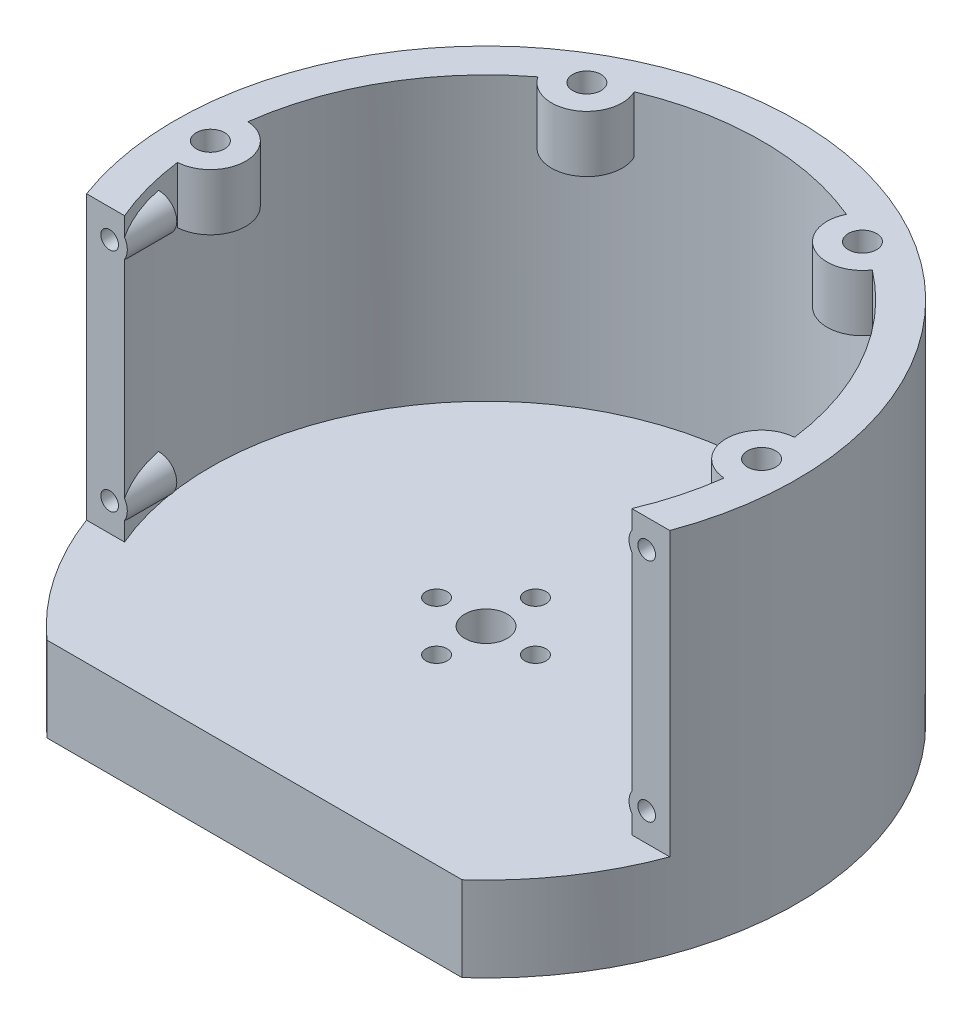
SolidWorks part; units mm, degrees
ref_plane "Спереди" through (0, 0, 0) normal (0, 0, 1) x (1, 0, 0)
ref_plane "Сверху" through (0, 0, 0) normal (0, 1, 0) x (1, 0, 0)
ref_plane "Справа" through (0, 0, 0) normal (1, 0, 0) x (0, 0, -1)
sketch "Эскиз6" plane through (0, 0, 0) normal (1, 0, 0) x (0, 0, -1)
  line L0 (26, 0) -> (44, 0)
  line L1 (0, 0) -> (0, 77.627) construction
  line L2 (44, 0) -> (44, 52)
  line L3 (44, 52) -> (39, 52)
  line L4 (39, 52) -> (39, 12)
  line L5 (39, 12) -> (0, 12)
  line L6 (0, 12) -> (0, 7)
  line L7 (0, 7) -> (26, 7)
  line L8 (26, 7) -> (26, 0)
  dimension "D1" = 5
  dimension "D2" = 26
  dimension "D3" = 52
  dimension "D4" = 44
  dimension "D5" = 7
revolve "Повернуть1" add sketch "Эскиз6" angle 360 about L1
sketch "Эскиз9" plane through (0, 0, 0) normal (0, 1, 0) x (1, 0, 0)
  circle A0 centre (0, 0) radius 3
  circle A1 centre (0, 0) radius 7 construction
  circle A2 centre (0, 7) radius 1.5
  circle A3 centre (7, 0) radius 1.5
  circle A4 centre (0, -7) radius 1.5
  circle A5 centre (-7, 0) radius 1.5
  point P15 (0, 0)
  dimension "D1" = 4
extrude "Вырез-Вытянуть1" cut sketch "Эскиз9" along normal up to surface (12 mm away) from offset 7 up to face at (0, 12, -39)
ref_plane "Плоскость1" through (0, 0, 45) normal (0, 0, 1) x (1, 0, 0)
sketch "Эскиз14" plane through (0, 0, 0) normal (0, 1, 0) x (1, 0, 0)
  line L0 (36, -15) -> (-36, -15)
  arc A0 (36, -15) -> (-36, -15) centre (0, 0) cw
  circle A1 centre (0, 0) radius 39 construction
  circle A2 centre (0, 0) radius 39 construction
  dimension "D1" = 15
extrude "Бобышка-Вытянуть6" [suppressed] add sketch "Эскиз14" against normal up to surface (38 mm away) from offset 50
sketch "Эскиз17" plane through (0, 0, 45) normal (0, 0, 1) x (1, 0, 0)
  line L0 (36, 52) -> (-36, 52)
  line L1 (44, 52) -> (-44, 52) construction
  line L2 (-37.4166, 0) -> (37.4166, 0)
  line L3 (-44, 0) -> (44, 0) construction
  arc A0 (-36, 52) -> (-37.4166, 0) centre (0, 25) ccw
  arc A1 (37.4166, 0) -> (36, 52) centre (0, 25) ccw
  dimension "D1" = 90
  dimension "D2" = 25
extrude "Бобышка-Вытянуть15" [suppressed] add sketch "Эскиз17" against normal up to surface (30 mm away)
sketch "Эскиз11" plane through (0, 0, 45) normal (0, 0, 1) x (1, 0, 0)
  line L0 (-44, 0) -> (44, 0) construction
  line L1 (-30, 35) -> (10, 35)
  line L2 (-30, 35) -> (-30, 15)
  line L3 (-30, 15) -> (10, 15)
  line L4 (10, 35) -> (10, 15)
  dimension "D1" = 20
  dimension "D2" = 40
  dimension "D3" = 15
  dimension "D4" = 30
extrude "Вырез-Вытянуть2" [suppressed] cut sketch "Эскиз11" against normal blind 50 and the other way blind 150
sketch "Эскиз15" plane through (0, 0, 45) normal (0, 0, 1) x (1, 0, 0)
  line L1 (-37, 37) -> (17, 37)
  line L2 (-37, 37) -> (-37, 17)
  line L3 (-37, 17) -> (17, 17)
  line L4 (17, 37) -> (17, 17)
  line L6 (44, 52) -> (-44, 52) construction
  dimension "D1" = 54
  dimension "D2" = 20
  dimension "D3" = 15
  dimension "D4" = 37
extrude "Вырез-Вытянуть5" [suppressed] cut sketch "Эскиз15" against normal blind 27 from offset 28 offset against normal yes
sketch "Эскиз19" plane through (0, 0, 45) normal (0, 0, 1) x (1, 0, 0)
  circle A0 centre (0, 25) radius 12
  dimension "D1" = 24
extrude "Вырез-Вытянуть7" [suppressed] cut sketch "Эскиз19" against normal up to surface and the other way blind 5
sketch "Эскиз20" [suppressed] plane through (0, 0, 0) normal (0, 1, 0) x (1, 0, 0)
  line L0 (-45, -30) -> (45, -30)
  line L1 (-45, -45) -> (-45, -30)
  line L2 (-45, 0) -> (-45, -45) construction
  line L3 (-45, -45) -> (45, -45)
  line L4 (37.4166, -45) -> (45, -45) construction
  line L5 (45, -45) -> (45, -30)
  line L6 (45, -45) -> (45, 0) construction
  dimension "D1" = 15
extrude "Вырез-Вытянуть8" [suppressed] cut sketch "Эскиз20" along normal blind 50
sketch "Эскиз21" plane through (0, 0, 0) normal (0, 1, 0) x (1, 0, 0)
  line L0 (41.2692, -15.2595) -> (-41.2692, -15.2595)
  arc A0 (41.2692, -15.2595) -> (-41.2692, -15.2595) centre (0, 0) cw
  dimension "D1" = 44
extrude "Вырез-Вытянуть9" cut sketch "Эскиз21" against normal blind 43 from offset 55
sketch "Эскиз22" plane through (0, 0, 15.2595) normal (0, 0, 1) x (1, 0, 0)
  line L0 (-44, 0) -> (44, 0) construction
  line L5 (-38, 48) -> (38, 48) construction
  line L6 (-38, 48) -> (-38, 16) construction
  line L7 (-38, 16) -> (38, 16) construction
  line L8 (38, 48) -> (38, 16) construction
  circle A3 centre (-38, 16) radius 2.5
  circle A4 centre (-38, 48) radius 2.5
  circle A5 centre (38, 48) radius 2.5
  circle A6 centre (38, 16) radius 2.5
  dimension "D1" = 32
  dimension "D2" = 76
  dimension "D3" = 16
  dimension "D4" = 5
  dimension "D6" = 5
  dimension "D7" = 5
  dimension "D8" = 5
  dimension "D5" = 38
sketch "Эскиз23" plane through (0, 12, 0) normal (0, 1, 0) x (1, 0, 0)
  line L0 (-29.3737, -32.7595) -> (29.3737, -32.7595)
  line L1 (41.2692, -15.2595) -> (35.8908, -15.2595) construction
  arc A0 (-41.2692, -15.2595) -> (41.2692, -15.2595) centre (0, 0) ccw construction
  arc A1 (29.3737, -32.7595) -> (-29.3737, -32.7595) centre (0, 0) cw
  dimension "D1" = 17.5
extrude "Вырез-Вытянуть11" cut sketch "Эскиз23" against normal through all
sketch "Эскиз25" plane through (0, 52, 0) normal (0, 1, 0) x (1, 0, 0)
  arc A0 (-38.6795, -4.9897) -> (-38.6795, 4.9897) centre (-39, 0) ccw
  arc A1 (35.8908, -15.2595) -> (-35.8908, -15.2595) centre (0, 0) ccw construction
  arc A2 (35.8908, -15.2595) -> (-35.8908, -15.2595) centre (0, 0) ccw construction
  arc A3 (-38.6795, 4.9897) -> (-38.6795, -4.9897) centre (0, 0) ccw
extrude "Бобышка-Вытянуть17" add sketch "Эскиз25" against normal blind 8
sketch "Эскиз26" plane through (0, 52, 0) normal (0, 1, 0) x (1, 0, 0)
  circle A0 centre (-39, 0) radius 2
  circle A1 centre (0, 0) radius 39 construction
  dimension "D1" = 4
extrude "Вырез-Вытянуть12" cut sketch "Эскиз26" against normal blind 5
pattern_circular "Круговой массив3" count 4 every 60 about axis through (0, 52, 0) along (0, -1, 0) of "Бобышка-Вытянуть17", "Вырез-Вытянуть12"
extrude "Бобышка-Вытянуть19" add sketch "Эскиз22" against normal blind 7
sketch "Эскиз28" plane through (0, 0, 15.2595) normal (0, 0, 1) x (1, 0, 0)
  line L5 (-38, 48) -> (38, 48) construction
  line L6 (-38, 48) -> (-38, 16) construction
  line L7 (-38, 16) -> (38, 16) construction
  line L8 (38, 48) -> (38, 16) construction
  circle A3 centre (-38, 16) radius 1.25
  circle A4 centre (-38, 48) radius 1.25
  circle A5 centre (38, 48) radius 1.25
  circle A6 centre (38, 16) radius 1.25
  dimension "D1" = 32
  dimension "D2" = 76
  dimension "D4" = 2.5
  dimension "D6" = 2.5
  dimension "D7" = 2.5
  dimension "D8" = 2.5
extrude "Вырез-Вытянуть13" cut sketch "Эскиз28" against normal blind 5
